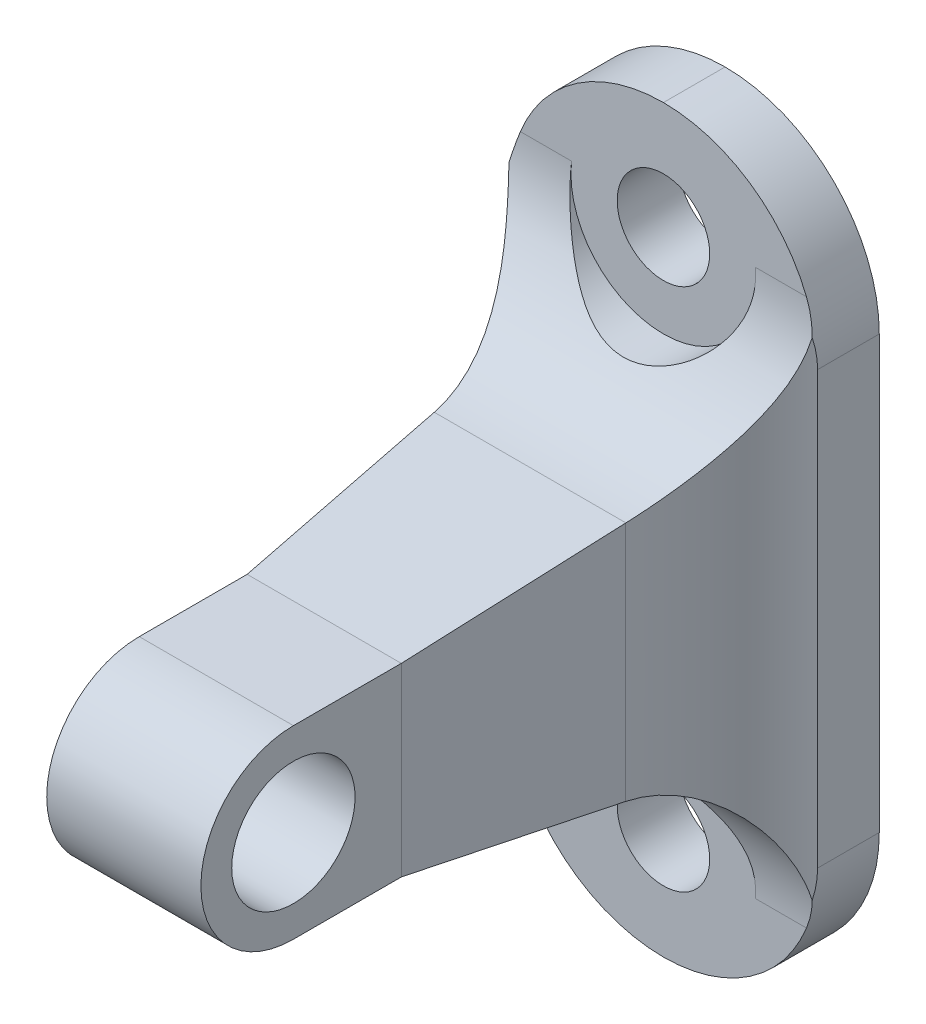
SolidWorks part; units mm, degrees
material "7075-T6, Płyta (SS)"
ref_plane "Płaszczyzna przednia" through (0, 0, 0) normal (0, 0, 1) x (1, 0, 0)
ref_plane "Płaszczyzna górna" through (0, 0, 0) normal (0, 1, 0) x (1, 0, 0)
ref_plane "Płaszczyzna prawa" through (0, 0, 0) normal (1, 0, 0) x (0, 0, -1)
sketch "Szkic1" plane through (0, 0, 0) normal (1, 0, 0) x (0, 0, -1)
  line L0 (0, -24) -> (0, 24)
  line L1 (0, -24) -> (-4, -24)
  line L2 (0, 24) -> (-4, 24)
  line L5 (-4, 9) -> (-4, 24)
  line L6 (-4, -9) -> (-4, -24)
  line L11 (-33, -6) -> (-26, -6)
  line L12 (-33, 6) -> (-26, 6)
  line L13 (-26, -6) -> (-4, -9)
  line L14 (-26, 6) -> (-4, 9)
  circle A0 centre (-33, 0) radius 4
  arc A2 (-33, 6) -> (-33, -6) centre (-33, 0) ccw
  dimension "D1" = 8
  dimension "D7" = 12
  dimension "D2" = 48
  dimension "D3" = 33
  dimension "D4" = 0
  dimension "D5" = 4
  dimension "D6" = 4
  dimension "D8" = 15
  dimension "D9" = 15
  dimension "D10" = 7
  dimension "D11" = 7
extrude "Dodanie-wyciągnięcie1" add sketch "Szkic1" along normal blind 20
sketch "Szkic2" plane through (0, 24, 0) normal (0, 1, 0) x (1, 0, 0)
  line L0 (10, -42.8877) -> (10, 7.2926) construction
  line L1 (5, -39) -> (5, -26)
  line L2 (0, -39) -> (20, -39) construction
  line L3 (20, -26) -> (0, -26) construction
  line L4 (5, -39) -> (15, -39)
  line L5 (15, -39) -> (15, -26)
  line L6 (0, -33) -> (0, -39) construction
  line L7 (20, -4) -> (17, -4)
  line L8 (20, -4) -> (0, -4) construction
  line L9 (17, -4) -> (15, -26)
  line L10 (0, -4) -> (3, -4)
  line L11 (3, -4) -> (5, -26)
  line L12 (20, -4) -> (20, -45.8373)
  line L13 (0, -4) -> (0, -45.8373)
  line L14 (0, -45.8373) -> (20, -45.8373)
  dimension "D1" = 10
  dimension "D2" = 5
  dimension "D3" = 5
  dimension "D4" = 3
  dimension "D5" = 3
extrude "Wytnij-wyciągnięcie1" cut sketch "Szkic2" against normal through all
fillet "Zaokrąglenie1" radius 10 4 edges at (20, 24, 2) (0, 24, 2) (0, -24, 2) (20, -24, 2)
fillet "Zaokrąglenie2" radius 15 2 edges at (17, 0, 4) (3, 0, 4)
fillet "Zaokrąglenie4" radius 10 2 edges at (10, -9, 4) (10, 9, 4)
sketch "Szkic3" plane through (0, 0, 4) normal (0, 0, 1) x (1, 0, 0)
  line L0 (0, 14) -> (0, -14) construction
  circle A0 centre (10, -17) radius 3
  circle A1 centre (10, 17) radius 3
  dimension "D1" = 6
  dimension "D2" = 6
  dimension "D3" = 34
  dimension "D4" = 17
  dimension "D5" = 10
  dimension "D6" = 10
extrude "Wytnij-wyciągnięcie2" cut sketch "Szkic3" against normal through all
sketch "Szkic4" plane through (0, 0, 0) normal (0, 0, 1) x (1, 0, 0)
  line L0 (0, 14) -> (0, -14) construction
  line L1 (10, -17) -> (10, 17) construction
  circle A0 centre (10, -17) radius 6
  circle A1 centre (10, 17) radius 6
  dimension "D1" = 12
  dimension "D2" = 12
  dimension "D3" = 34
  dimension "D4" = 10
  dimension "D5" = 10
  dimension "D6" = 17
extrude "Wytnij-wyciągnięcie4" cut sketch "Szkic4" along normal blind 20 from offset 4
